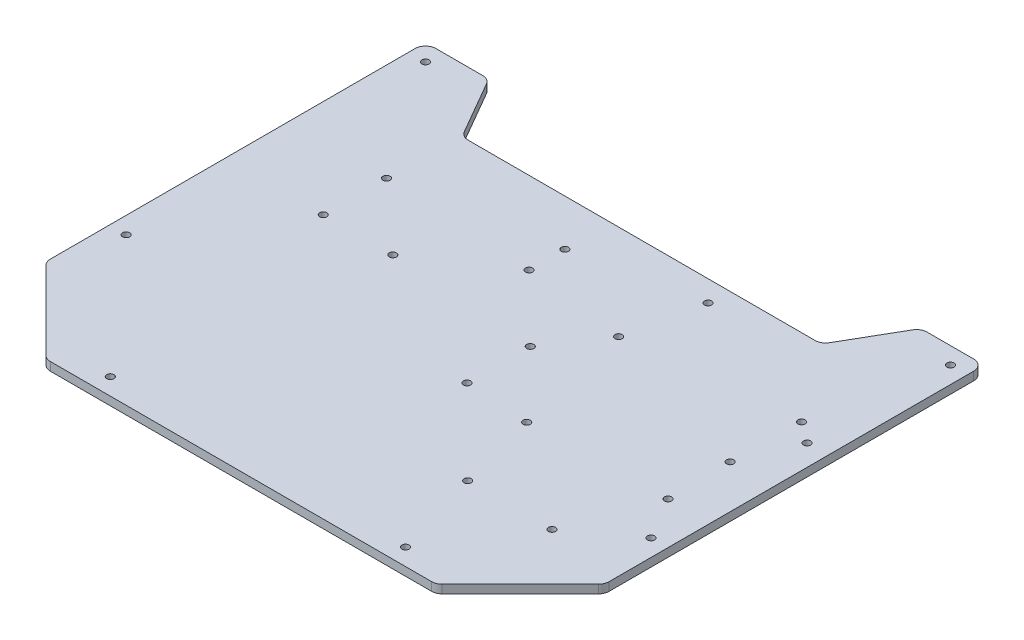
SolidWorks part; units mm, degrees
material "Acier non allié"
ref_plane "Front" through (0, 0, 0) normal (0, 0, 1) x (1, 0, 0)
ref_plane "Top" through (0, 0, 0) normal (0, 1, 0) x (1, 0, 0)
ref_plane "Right" through (0, 0, 0) normal (1, 0, 0) x (0, 0, -1)
sketch "Main scetch" plane through (0, 0, 0) normal (0, 1, 0) x (1, 0, 0)
  line L1 (0, 0) -> (132.5, 0) construction
  line L2 (0, 0) -> (0, 220) construction
  line L3 (0, 220) -> (132.5, 220) construction
  line L4 (132.5, 0) -> (132.5, 220) construction
  line L13 (-92.5, 0) -> (92.5, 0)
  line L14 (92.5, 0) -> (132.5, 40)
  line L15 (132.5, 40) -> (132.5, 220)
  line L16 (132.5, 220) -> (102.5, 220)
  line L17 (102.5, 220) -> (85.1795, 190)
  line L18 (85.1795, 190) -> (-85.1795, 190)
  line L19 (-102.5, 220) -> (-85.1795, 190)
  line L20 (-132.5, 220) -> (-102.5, 220)
  line L21 (-132.5, 40) -> (-132.5, 220)
  line L22 (-92.5, 0) -> (-132.5, 40)
  point P11 (0, 190)
  dimension "132.5" = 132.5
  dimension "D2" = 220
  dimension "D1" = 40
  dimension "D3" = 40
  dimension "D4" = 30
  dimension "D5" = 60
  dimension "D6" = 30
extrude "Main extrusion" add sketch "Main scetch" along normal blind 4
fillet "Congé1" radius 5 10 edges at (-132.5, 2, -40) (-92.5, 2, 0) (92.5, 2, 0) (132.5, 2, -40) (132.5, 2, -220) (102.5, 2, -220) (85.1795, 2, -190) (-85.1795, 2, -190) (-102.5, 2, -220) (-132.5, 2, -220)
sketch "Esquisse1" plane through (0, 4, 0) normal (0, 1, 0) x (1, 0, 0)
  line L0 (0, 0) -> (0, 218.5516) construction
  line L1 (132.5, 42.0711) -> (132.5, 215) construction
  line L2 (127.5, 220) -> (105.3868, 220) construction
  line L3 (-90.4289, 0) -> (90.4289, 0) construction
  circle A0 centre (70, 8) radius 1
  circle A1 centre (124.5, 70) radius 1
  circle A2 centre (124.5, 212) radius 1
  circle A3 centre (-124.5, 212) radius 1
  circle A4 centre (-124.5, 70) radius 1
  circle A5 centre (-70, 8) radius 1
  dimension "D1" = 2
  dimension "D2" = 2
  dimension "D3" = 2
  dimension "D4" = 8
  dimension "D5" = 8
  dimension "D6" = 8
  dimension "D7" = 8
  dimension "D8" = 70
  dimension "D9" = 70
extrude "Enlèv. mat.-Extru.1" cut sketch "Esquisse1" against normal through all
hole_wizard "Dégagement M31" positions "Esquisse2" profile "Esquisse3" hole size "M3" standard "ISO" end condition through all
sketch "Esquisse2" plane through (0, 4, 0) normal (0, 1, 0) x (1, 0, 0)
  point P0 (-124.5, 212)
  point P3 (-124.5, 70)
  point P6 (-70, 8)
  point P9 (70, 8)
  point P12 (124.5, 70)
  point P15 (124.5, 212)
sketch "Esquisse3" plane through (-124.5, 4, -212) normal (1, 0, 0) x (0, 0, 1)
  line L0 (0, 0) -> (0, 4)
  line L1 (0, 4) -> (1.7, 4)
  line L2 (1.7, 4) -> (1.7, 0)
  line L5 (1.7, 0) -> (0, 0)
  line L11 (0, -6.35) -> (0, 107.95) construction
  dimension "Diamètre du perçage jusqu'au prochain" = 3.4
  dimension "Profondeur du perçage jusqu'au prochain" = 4
sketch "Esquisse4" plane through (0, 4, 0) normal (0, 1, 0) x (1, 0, 0)
  line L0 (-132.5, 215) -> (-132.5, 42.0711) construction
  line L1 (-105.3868, 220) -> (-127.5, 220) construction
  line L2 (82.2927, 190) -> (-82.2927, 190) construction
  line L3 (132.5, 42.0711) -> (132.5, 215) construction
  line L4 (-90.4289, 0) -> (90.4289, 0) construction
  line L5 (127.5, 220) -> (105.3868, 220) construction
  circle A0 centre (-86, 125) radius 1
  circle A1 centre (-86, 155) radius 1
  circle A2 centre (-53, 125) radius 1
  circle A3 centre (-14.5, 151.1) radius 1
  circle A4 centre (-14.5, 168.1) radius 1
  circle A5 centre (41.5, 180) radius 1
  circle A6 centre (34.12, 145) radius 1
  circle A7 centre (112.5, 153.32) radius 1
  circle A8 centre (122.5, 146) radius 1
  circle A9 centre (112, 120) radius 1
  circle A10 centre (112.5, 90) radius 1
  circle A11 centre (17.2, 120) radius 1
  circle A12 centre (17.2, 90) radius 1
  circle A13 centre (47.5, 88) radius 1
  circle A14 centre (57.5, 50) radius 1
  circle A15 centre (97.5, 50) radius 1
  dimension "D1" = 2
  dimension "D4" = 2
  dimension "D6" = 2
  dimension "D8" = 2
  dimension "D11" = 2
  dimension "D13" = 2
  dimension "D16" = 2
  dimension "D19" = 2
  dimension "D24" = 2
  dimension "D25" = 2
  dimension "D28" = 2
  dimension "D30" = 2
  dimension "D32" = 2
  dimension "D36" = 2
  dimension "D37" = 2
  dimension "D40" = 2
  dimension "D2" = 46.5
  dimension "D3" = 95
  dimension "D5" = 65
  dimension "D7" = 79.5
  dimension "D9" = 38.9
  dimension "D10" = 118
  dimension "D12" = 21.9
  dimension "D14" = 174
  dimension "D15" = 10
  dimension "D17" = 166.62
  dimension "D18" = 45
  dimension "D20" = 20
  dimension "D21" = 66.68
  dimension "D22" = 10
  dimension "D23" = 74
  dimension "D26" = 20.5
  dimension "D27" = 100
  dimension "D29" = 30
  dimension "D31" = 115.3
  dimension "D33" = 115.3
  dimension "D34" = 132
  dimension "D35" = 85
  dimension "D38" = 50
  dimension "D39" = 75
  dimension "D41" = 35
extrude "Enlèv. mat.-Extru.2" cut sketch "Esquisse4" against normal through all
hole_wizard "Dégagement M32" positions "Esquisse5" profile "Esquisse6" hole size "M3" standard "ISO" end condition through all
sketch "Esquisse5" plane through (0, 4, 0) normal (0, 1, 0) x (1, 0, 0)
  point P0 (-86, 155)
  point P3 (-86, 125)
  point P6 (-53, 125)
  point P9 (17.2, 120)
  point P12 (-14.5, 151.1)
  point P15 (-14.5, 168.1)
  point P18 (34.12, 145)
  point P21 (41.5, 180)
  point P24 (112.5, 153.32)
  point P27 (122.5, 146)
  point P30 (112, 120)
  point P33 (112.5, 90)
  point P36 (47.5, 88)
  point P39 (17.2, 90)
  point P42 (57.5, 50)
  point P45 (97.5, 50)
sketch "Esquisse6" plane through (-86, 4, -155) normal (1, 0, 0) x (0, 0, 1)
  line L0 (0, 0) -> (0, 4)
  line L1 (0, 4) -> (1.7, 4)
  line L2 (1.7, 4) -> (1.7, 0)
  line L5 (1.7, 0) -> (0, 0)
  line L11 (0, -6.35) -> (0, 107.95) construction
  dimension "Diamètre du perçage jusqu'au prochain" = 3.4
  dimension "Profondeur du perçage jusqu'au prochain" = 4
equation "\"WIDTH\"= 300mm'Total width of the robot"
equation "\"LENGTH\"= 220mm'Total length of the robot"
equation "\"D2@Main scetch\" = \"LENGTH\""
equation "\"CUT_DEPTH\"= 45mm'Depth of the cut on the edges of the plate"
equation "\"Plate_th\"= 3mm'Thickness of the plate"
equation "\"D1\"= \"Plate_th\""
